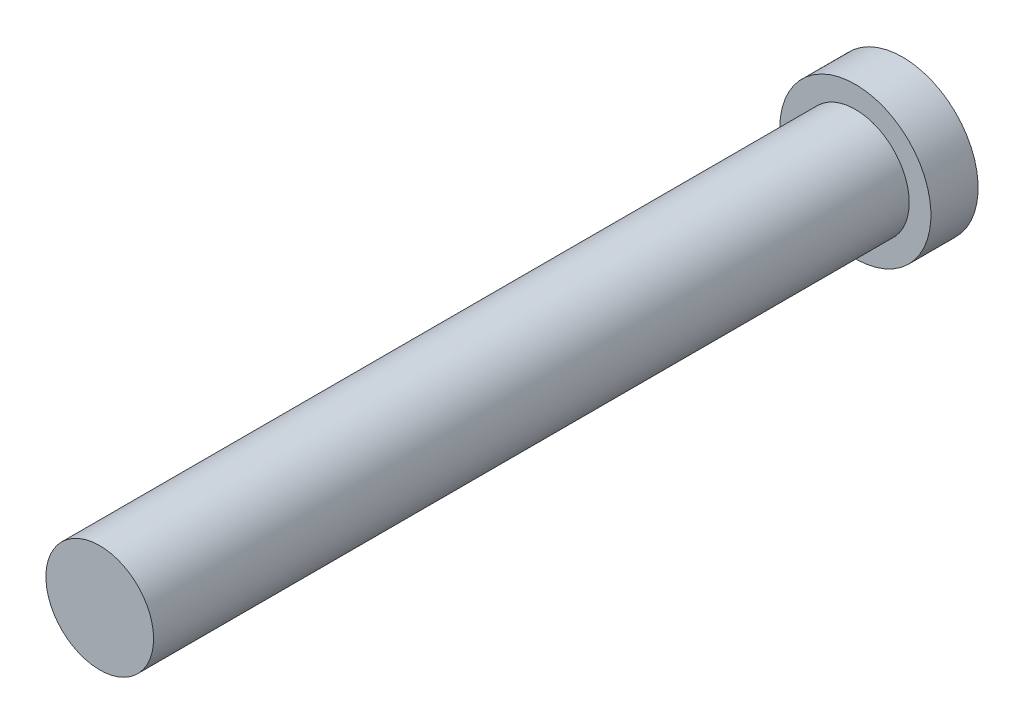
SolidWorks part; units mm, degrees
ref_plane "Front Plane" through (0, 0, 0) normal (0, 0, 1) x (1, 0, 0)
ref_plane "Top Plane" through (0, 0, 0) normal (0, 1, 0) x (1, 0, 0)
ref_plane "Right Plane" through (0, 0, 0) normal (1, 0, 0) x (0, 0, -1)
sketch "Sketch1" plane through (0, 0, 0) normal (0, 0, 1) x (1, 0, 0)
  circle A0 centre (0, 0) radius 2.85
  dimension "D1" = 5.7
extrude "Boss-Extrude1" add sketch "Sketch1" along normal blind 40
sketch "Sketch2" plane through (0, 0, 0) normal (0, 0, -1) x (-1, 0, 0)
  circle A0 centre (0, 0) radius 4
  dimension "D1" = 8
extrude "Boss-Extrude2" add sketch "Sketch2" along normal blind 5
sketch "Sketch3" plane through (0, 0, 0) normal (1, 0, 0) x (0, 0, -1)
  line L0 (0, -4) -> (5, -4) construction
  line L1 (5, 4) -> (2.5, 4)
  line L2 (5, 4) -> (5, -4)
  line L3 (5, -4) -> (2.5, -4)
  line L4 (2.5, 4) -> (2.5, -4)
extrude "Cut-Extrude1" cut sketch "Sketch3" against normal blind 10 and the other way blind 10
